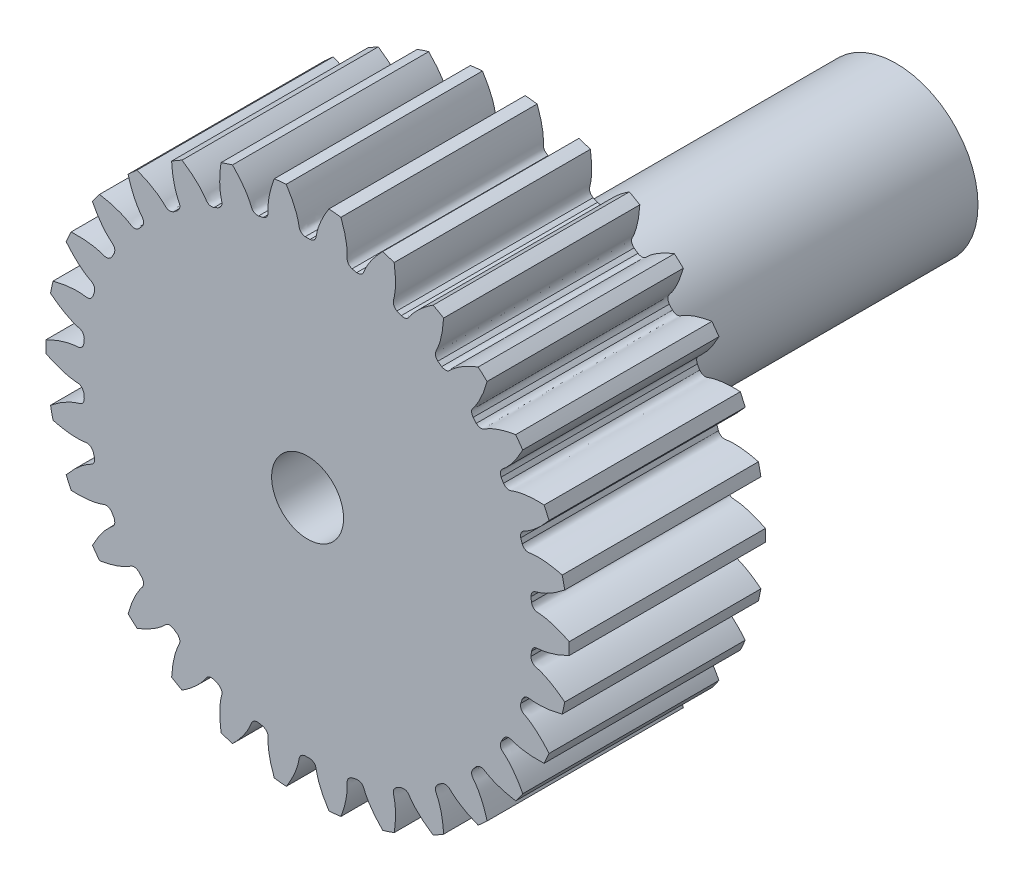
SolidWorks part; units mm, degrees
ref_plane "前视基准面" through (0, 0, 0) normal (0, 0, 1) x (1, 0, 0)
ref_plane "上视基准面" through (0, 0, 0) normal (0, 1, 0) x (1, 0, 0)
ref_plane "右视基准面" through (0, 0, 0) normal (1, 0, 0) x (0, 0, -1)
sketch "草图1" plane through (0, 0, 0) normal (0, 0, 1) x (1, 0, 0)
  circle A0 centre (0, 0) radius 16
extrude "凸台-拉伸1" add sketch "草图1" along normal blind 12
ref_axis "基准轴1" through (0, 0, 12) along (0, 0, -1)
sketch "草图2" plane through (0, 0, 0) normal (0, 0, 1) x (1, 0, 0)
  line L0 (0, 0) -> (0, 16) construction
  circle A0 centre (0, 0) radius 16 construction
  arc A1 (0.1456, 13.7492) -> (-0.1456, 13.7492) centre (0, 0) ccw
  arc A2 (3.3663, 18.1906) -> (-3.3663, 18.1906) centre (0, 0) ccw
  spline S0 degree 3 poles (0.1456, 13.7492) (0.5082, 13.813) (0.5103, 14.0471) (0.559, 14.2886) (0.57, 14.3381) (0.5832, 14.3929) (0.5991, 14.4529) (0.6176, 14.518) (0.6391, 14.588) (0.6638, 14.663) (0.6918, 14.7428) (0.7234, 14.8273) (0.7588, 14.9164) (0.7981, 15.01) (0.8416, 15.1079) (0.8894, 15.21) (0.9417, 15.3163) (0.9987, 15.4264) (1.0606, 15.5404) (1.1276, 15.658) (1.1998, 15.779) (1.2774, 15.9034) (1.3605, 16.031) (1.4494, 16.1615) (1.5441, 16.2948) (1.6448, 16.4307) (1.7516, 16.569) (1.8647, 16.7096) (1.9843, 16.8522) (2.1103, 16.9966) (2.2431, 17.1427) (2.3825, 17.2901) (2.5289, 17.4388) (2.6823, 17.5884) (2.8427, 17.7389) (3.0689, 17.9426) (3.2453, 18.0921) (3.3663, 18.1906) knots 0 0 0 0 0.115324 0.123413 0.132512 0.142623 0.153745 0.165878 0.179022 0.193177 0.208343 0.22452 0.241708 0.259907 0.279117 0.299338 0.320571 0.342814 0.366068 0.390334 0.41561 0.441898 0.469196 0.497506 0.526827 0.557158 0.588501 0.620855 0.65422 0.688595 0.723982 0.76038 0.797789 0.836209 0.87564 0.916083 1 1 1 1
  spline S1 degree 3 poles (-0.1456, 13.7492) (-0.5082, 13.813) (-0.5103, 14.0471) (-0.559, 14.2886) (-0.57, 14.3381) (-0.5832, 14.3929) (-0.5991, 14.4529) (-0.6176, 14.518) (-0.6391, 14.588) (-0.6638, 14.663) (-0.6918, 14.7428) (-0.7234, 14.8273) (-0.7588, 14.9164) (-0.7981, 15.01) (-0.8416, 15.1079) (-0.8894, 15.21) (-0.9417, 15.3163) (-0.9987, 15.4264) (-1.0606, 15.5404) (-1.1276, 15.658) (-1.1998, 15.779) (-1.2774, 15.9034) (-1.3605, 16.031) (-1.4494, 16.1615) (-1.5441, 16.2948) (-1.6448, 16.4307) (-1.7516, 16.569) (-1.8647, 16.7096) (-1.9843, 16.8522) (-2.1103, 16.9966) (-2.2431, 17.1427) (-2.3825, 17.2901) (-2.5289, 17.4388) (-2.6823, 17.5884) (-2.8427, 17.7389) (-3.0689, 17.9426) (-3.2453, 18.0921) (-3.3663, 18.1906) knots 0 0 0 0 0.115324 0.123413 0.132512 0.142623 0.153745 0.165878 0.179022 0.193177 0.208343 0.22452 0.241708 0.259907 0.279117 0.299338 0.320571 0.342814 0.366068 0.390334 0.41561 0.441898 0.469196 0.497506 0.526827 0.557158 0.588501 0.620855 0.65422 0.688595 0.723982 0.76038 0.797789 0.836209 0.87564 0.916083 1 1 1 1
extrude "切除-拉伸1" cut sketch "草图2" along normal through all
pattern_circular "阵列(圆周)1" count 30 every 12 about axis through (0, 0, 12) along (0, 0, -1) of "切除-拉伸1"
sketch "草图3" plane through (0, 0, 0) normal (0, 0, 1) x (1, 0, 0)
  circle A0 centre (0, 0) radius 15 construction
  dimension "Dn" = 30
sketch "草图4" plane through (0, 0, 12) normal (0, 0, 1) x (1, 0, 0)
  circle A0 centre (0, 0) radius 5
  dimension "D1" = 10
extrude "切除-拉伸2" cut sketch "草图4" against normal through all both and the other way through all
sketch "草图6" plane through (0, 0, 12) normal (0, 0, 1) x (1, 0, 0)
  circle A0 centre (0, 0) radius 5
  circle A1 centre (0, 0) radius 2.2
  dimension "D1" = 4.4
  dimension "D2" = 10
extrude "凸台-拉伸2" add sketch "草图6" against normal blind 36
